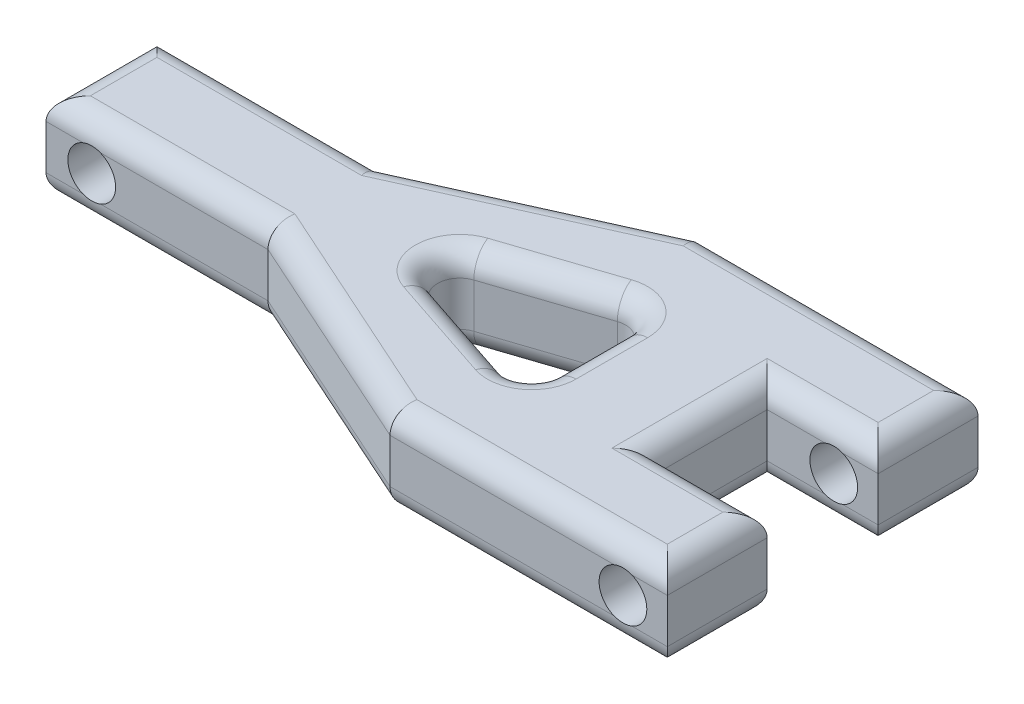
SolidWorks part; units mm, degrees
ref_plane "Front Plane" through (0, 0, 0) normal (0, 0, 1) x (1, 0, 0)
ref_plane "Top Plane" through (0, 0, 0) normal (0, 1, 0) x (1, 0, 0)
ref_plane "Right Plane" through (0, 0, 0) normal (1, 0, 0) x (0, 0, -1)
sketch "Sketch1" plane through (0, 0, 0) normal (0, 1, 0) x (1, 0, 0)
  line L1 (26.9692, -14.5231) -> (-38.0308, -14.5231)
  line L2 (26.9692, -14.5231) -> (26.9692, 13.4769)
  line L3 (26.9692, 13.4769) -> (-38.0308, 13.4769)
  line L4 (-38.0308, -14.5231) -> (-38.0308, 13.4769)
  dimension "D1" = 65
  dimension "D2" = 28
extrude "Boss-Extrude1" add sketch "Sketch1" along normal blind 8
sketch "Sketch2" plane through (0, 8, 0) normal (0, 1, 0) x (1, 0, 0)
  line L0 (26.9692, -14.5231) -> (26.9692, 13.4769) construction
  line L1 (26.9692, 4.4769) -> (16.9692, 4.4769)
  line L2 (26.9692, 4.4769) -> (26.9692, -5.5231)
  line L3 (26.9692, -5.5231) -> (16.9692, -5.5231)
  line L4 (16.9692, 4.4769) -> (16.9692, -5.5231)
  line L5 (26.9692, 13.4769) -> (-38.0308, 13.4769) construction
  line L6 (-38.0308, -14.5231) -> (26.9692, -14.5231) construction
  dimension "D1" = 10
  dimension "D2" = 10
  dimension "D3" = 9
  dimension "D4" = 9
extrude "Cut-Extrude1" cut sketch "Sketch2" against normal blind 10
sketch "Sketch3" plane through (0, 0, 14.5231) normal (0, 0, 1) x (1, 0, 0)
  line L0 (-38.0308, 8) -> (26.9692, 8) construction
  line L2 (26.9692, 8) -> (26.9692, 0) construction
  circle A0 centre (22.9692, 4) radius 2.15
  dimension "D1" = 4.3
  dimension "D2" = 4
  dimension "D3" = 4
extrude "Cut-Extrude2" cut sketch "Sketch3" against normal through all
sketch "Sketch5" plane through (0, 8, 0) normal (0, 1, 0) x (1, 0, 0)
  line L0 (-18.0224, 4.4769) -> (1.9776, 13.4769)
  line L1 (-38.0308, 13.4769) -> (-18.0224, 13.4769)
  line L2 (-38.0308, 13.4769) -> (-38.0308, 4.4769)
  line L3 (-38.0308, 4.4769) -> (-18.0224, 4.4769)
  line L4 (-18.0224, 13.4769) -> (-18.0224, 4.4769)
  line L5 (-38.0308, -14.5231) -> (-18.0224, -14.5231)
  line L6 (-38.0308, -14.5231) -> (-38.0308, -5.5231)
  line L7 (-38.0308, -5.5231) -> (-18.0224, -5.5231)
  line L8 (-18.0224, -14.5231) -> (-18.0224, -5.5231)
  line L9 (26.9692, 13.4769) -> (-38.0308, 13.4769) construction
  line L10 (-18.0224, -5.5231) -> (1.9776, -14.5231)
  line L11 (-38.0308, -14.5231) -> (26.9692, -14.5231) construction
  line L12 (1.9776, -14.5231) -> (-18.0224, -14.5231)
  line L13 (1.9776, 13.4769) -> (-18.0224, 13.4769)
  line M10 (26.9692, 13.4769) -> (-38.0308, 13.4769)
  line M11 (-38.0308, 13.4769) -> (-38.0308, -14.5231)
  line M12 (-38.0308, -14.5231) -> (26.9692, -14.5231)
  dimension "D1" = 10
  dimension "D2" = 9
  dimension "D3" = 20
  dimension "D4" = 20
extrude "Cut-Extrude4" cut sketch "Sketch5" against normal through all contours L4 L3 M10 M11 | L4 L0 M10 | L10 L8 M12 | L8 L7 M12 M11 region at (-11.3557, 8, -10.4769) region at (-28.0266, 8, 10.0231) region at (-28.0266, 8, -8.9769) region at (-11.3557, 8, 11.5231)
fillet "Fillet1" radius 2 24 edges at (-28.0266, 0, 5.5231) (-8.0224, 0, 10.0231) (14.4734, 0, 14.5231) (26.9692, 0, 10.0231) (21.9692, 0, 5.5231) (16.9692, 0, 0.5231) (21.9692, 0, -4.4769) (26.9692, 0, -8.9769) (14.4734, 0, -13.4769) (-8.0224, 0, -8.9769) (-28.0266, 0, -4.4769) (-38.0308, 0, 0.5231) (-8.0224, 8, -8.9769) (14.4734, 8, -13.4769) (26.9692, 8, -8.9769) (21.9692, 8, -4.4769) (16.9692, 8, 0.5231) (21.9692, 8, 5.5231) (26.9692, 8, 10.0231) (14.4734, 8, 14.5231) (-8.0224, 8, 10.0231) (-28.0266, 8, 5.5231) (-38.0308, 8, 0.5231) (-28.0266, 8, -4.4769)
sketch "Sketch8" plane through (0, 0, -4.4769) normal (0, 0, -1) x (-1, 0, 0)
  circle A0 centre (33.9097, 4) radius 2.15
  dimension "D1" = 4.3
extrude "Cut-Extrude5" cut sketch "Sketch8" against normal through all
sketch "Sketch9" plane through (0, 8, 0) normal (0, 1, 0) x (1, 0, 0)
  line L0 (-12.0755, -0.5231) -> (5.9692, -6.5231)
  line L1 (5.9692, -6.5231) -> (5.9692, 5.4769)
  line L2 (5.9692, 5.4769) -> (-12.0755, -0.5231)
  line L3 (1.9776, 13.4769) -> (22.1802, 13.4769) construction
  line L4 (22.1802, -14.5231) -> (1.9776, -14.5231) construction
  line L5 (1.9776, -14.5231) -> (-18.0224, -5.5231) construction
  line L6 (-18.0224, 4.4769) -> (1.9776, 13.4769) construction
  line L7 (14.9692, -7.5231) -> (14.9692, 6.4769) construction
  dimension "D1" = 8
  dimension "D2" = 8
  dimension "D3" = 7
  dimension "D4" = 7
  dimension "D5" = 9
extrude "Cut-Extrude6" cut sketch "Sketch9" against normal blind 10
fillet "Fillet2" radius 2 9 edges at (5.9692, 0, 0.5231) (5.9692, 8, 0.5231) (-3.0531, 0, 3.5231) (5.9692, 4, 6.5231) (-3.0531, 8, 3.5231) (-3.0531, 0, -2.4769) (-12.0755, 4, 0.5231) (-3.0531, 8, -2.4769) (5.9692, 4, -5.4769)
